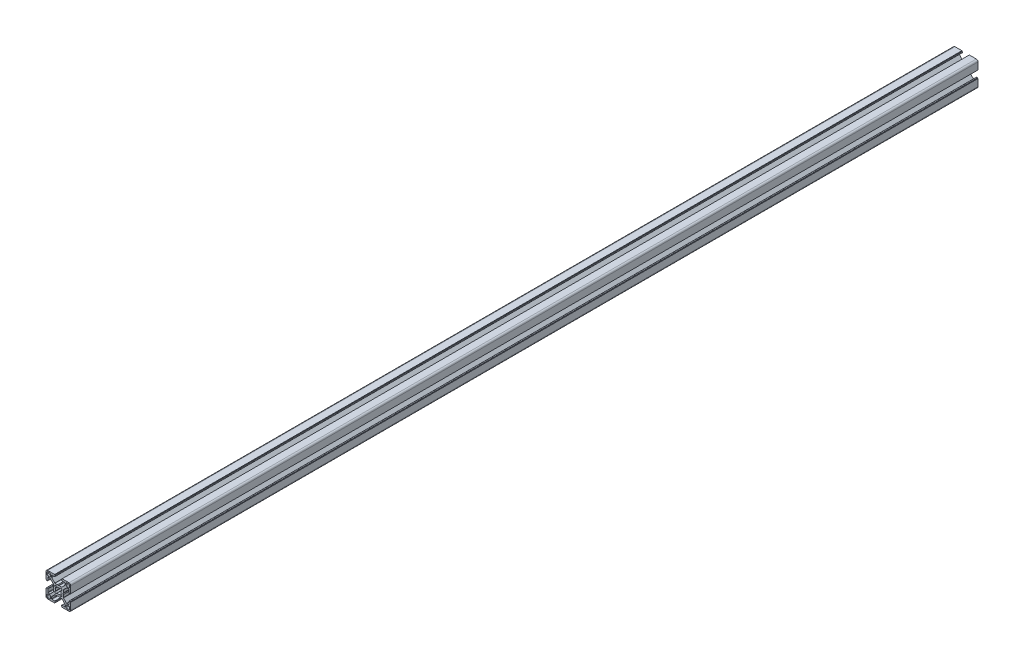
SolidWorks part; units mm, degrees
ref_plane "Front Plane" through (0, 0, 0) normal (0, 0, 1) x (1, 0, 0)
ref_plane "Top Plane" through (0, 0, 0) normal (0, 1, 0) x (1, 0, 0)
ref_plane "Right Plane" through (0, 0, 0) normal (1, 0, 0) x (0, 0, -1)
sketch "Sketch1" plane through (0, 0, 0) normal (0, 0, 1) x (1, 0, 0)
  line L0 (-15, 0) -> (15, 0) construction
  line L1 (0, -15) -> (0, 15) construction
  line L2 (-4.5, 15) -> (4.5, 15) construction
  line L3 (-4, -15) -> (4, -15) construction
  line L4 (-4.5, 15) -> (-4.5, 14.5)
  line L5 (-4.5, 14.5) -> (-4, 14.5)
  line L6 (-4, 14.5) -> (-4, 13.29)
  line L7 (-4.5, 12.79) -> (-7.7675, 12.79)
  line L8 (-8.2675, 12.29) -> (-8.2675, 10.2707)
  line L9 (-8.1211, 9.9171) -> (-4.3504, 6.1464)
  line L10 (-3.9968, 6) -> (0, 6)
  line L11 (0, 0) -> (-15, 15) construction
  line L12 (-4.5, 15) -> (-12.968, 15)
  line L14 (-12.705, 9.5135) -> (-10.5135, 9.5135)
  line L15 (-13.705, 10.5135) -> (-13.705, 12.705)
  line L16 (-12.705, 13.705) -> (-10.5135, 13.705)
  line L17 (-9.5135, 10.5135) -> (-9.5135, 12.705)
  line L18 (-13.705, 9.5135) -> (-9.5135, 13.705) construction
  line L19 (-13.705, 13.705) -> (-9.5135, 9.5135) construction
  line L20 (-3.1568, 4.5038) -> (-1.5303, 3.1477) construction
  line L21 (-4.5038, 3.1568) -> (-3.1477, 1.5303) construction
  line L22 (-6, 3.9968) -> (-6, 0)
  line L23 (-9.9171, 8.1211) -> (-6.1464, 4.3504)
  line L24 (-15, 4.5) -> (-15, 12.968)
  line L25 (-12.29, 8.2675) -> (-10.2707, 8.2675)
  line L26 (-12.79, 4.5) -> (-12.79, 7.7675)
  line L27 (-14.5, 4) -> (-13.29, 4)
  line L28 (-14.5, 4.5) -> (-14.5, 4)
  line L29 (-15, 4.5) -> (-14.5, 4.5)
  circle A0 centre (0, 0) radius 3.5
  arc A1 (-12.968, 15) -> (-15, 12.968) centre (-12.968, 12.968) ccw
  circle A2 centre (0, 0) radius 5.5 construction
  arc A3 (-10.5135, 9.5135) -> (-9.5135, 10.5135) centre (-10.5135, 10.5135) ccw
  arc A4 (-13.705, 12.705) -> (-12.705, 13.705) centre (-12.705, 12.705) cw
  arc A5 (-10.5135, 13.705) -> (-9.5135, 12.705) centre (-10.5135, 12.705) cw
  arc A6 (-12.705, 9.5135) -> (-13.705, 10.5135) centre (-12.705, 10.5135) cw
  arc A7 (-12.79, 4.5) -> (-13.29, 4) centre (-13.29, 4.5) cw
  arc A8 (-12.29, 8.2675) -> (-12.79, 7.7675) centre (-12.29, 7.7675) ccw
  arc A9 (-9.9171, 8.1211) -> (-10.2707, 8.2675) centre (-10.2707, 7.7675) ccw
  arc A10 (-6, 3.9968) -> (-6.1464, 4.3504) centre (-6.5, 3.9968) ccw
  arc A11 (-4.3504, 6.1464) -> (-3.9968, 6) centre (-3.9968, 6.5) ccw
  arc A12 (-4, 13.29) -> (-4.5, 12.79) centre (-4.5, 13.29) cw
  arc A13 (-7.7675, 12.79) -> (-8.2675, 12.29) centre (-7.7675, 12.29) ccw
  arc A14 (-8.2675, 10.2707) -> (-8.1211, 9.9171) centre (-7.7675, 10.2707) ccw
  point P4 (0, 0)
  point P8 (0, 0)
  point P13 (0, 15)
  point P15 (0, -15)
  point P16 (0, 6)
  point P23 (-11.6092, 11.6093)
  point P26 (0, 6)
  point P62 (-12.79, 4)
  point P65 (-12.79, 8.2675)
  point P68 (-10.0636, 8.2675)
  point P71 (-6, 4.2039)
  point P74 (-4.2039, 6)
  point P77 (-4, 12.79)
  point P80 (-8.2675, 12.79)
  point P83 (-8.2675, 10.0636)
  dimension "Center Hole Diameter" = 7
  dimension "D11" = 2.032
  dimension "D9" = 11
  dimension "D13" = 1
  dimension "D14" = 0.5
  dimension "Rail Height" = 30
  dimension "Rail Width" = 30
  dimension "T-Slot Width" = 8
  dimension "T-Slot Depth" = 9
  dimension "D1" = 9
  dimension "D2" = 45
  dimension "D3" = 8
  dimension "D4" = 2.21
  dimension "D5" = 16.535
  dimension "D7" = 2.54
  dimension "D6" = 1.295
  dimension "D8" = 1.246
  dimension "D10" = 10.36
  dimension "D12" = 1.905
sketch "Sketch2" plane through (0, 0, 0) normal (1, 0, 0) x (0, 0, -1)
  line L0 (-76.2, 0) -> (76.2, 0) construction
  line L2 (0, -15) -> (0, 15) construction
  line L3 (0, -15) -> (0, 15) construction
  line L4 (-76.2, -15) -> (-76.2, 15) construction
  line L5 (76.2, -15) -> (76.2, 15) construction
  point P0 (-38.7, 0)
  point P3 (0, 0)
  point P4 (38.7, 0)
  point P12 (-76.2, 0)
  point P14 (76.2, 0)
  dimension "Length" = 152.4
  dimension "D1" = 37.5
sketch "Sketch3" plane through (0, 0, 0) normal (0, 0, 1) x (1, 0, 0)
  line L0 (-4.5038, 3.1568) -> (-3.1477, 1.5303)
  line L1 (0, 3.5) -> (0, 5.5)
  line L2 (-5.5, 0) -> (-3.5, 0)
  line L7 (-6, 3.9968) -> (-6, 0) construction
  line L31 (-9.9171, 8.1211) -> (-6.1464, 4.3504) construction
  line L117 (-12.29, 8.2675) -> (-10.2707, 8.2675) construction
  line L118 (-12.79, 4.5) -> (-12.79, 7.7675) construction
  line L157 (-12.705, 9.5135) -> (-10.5135, 9.5135)
  line L158 (-9.5135, 10.5135) -> (-9.5135, 12.705)
  line L163 (-10.5135, 13.705) -> (-12.705, 13.705)
  line L164 (-13.705, 12.705) -> (-13.705, 10.5135)
  line L165 (-12.705, 9.5135) -> (-10.5135, 9.5135)
  line L166 (-9.5135, 10.5135) -> (-9.5135, 12.705)
  line L167 (-10.5135, 13.705) -> (-12.705, 13.705)
  line L168 (-13.705, 12.705) -> (-13.705, 10.5135)
  line L169 (-14.5, 4) -> (-13.29, 4) construction
  line L170 (-14.5, 4.5) -> (-14.5, 4) construction
  line L171 (-15, 4.5) -> (-14.5, 4.5) construction
  line L172 (-15, 4.5) -> (-15, 12.968) construction
  line L173 (-4.5, 15) -> (-12.968, 15) construction
  line L174 (-4.5, 15) -> (-4.5, 14.5) construction
  line L175 (-4.5, 14.5) -> (-4, 14.5) construction
  line L176 (-4, 14.5) -> (-4, 13.29) construction
  line L177 (-4.5, 12.79) -> (-7.7675, 12.79) construction
  line L178 (-8.2675, 12.29) -> (-8.2675, 10.2707) construction
  line L179 (-8.1211, 9.9171) -> (-4.3504, 6.1464) construction
  line L180 (-3.9968, 6) -> (0, 6) construction
  line L181 (-6, 3.9968) -> (-6, 0.866)
  line L182 (-9.9171, 8.1211) -> (-6.1464, 4.3504)
  line L183 (-12.29, 8.2675) -> (-10.2707, 8.2675)
  line L184 (-12.79, 4.5) -> (-12.79, 7.7675)
  line L185 (-14.5, 4) -> (-13.29, 4)
  line L186 (-14.5, 4.5) -> (-14.5, 4)
  line L187 (-15, 4.5) -> (-14.5, 4.5)
  line L188 (-15, 4.5) -> (-15, 12.968)
  line L189 (-4.5, 15) -> (-12.968, 15)
  line L190 (-4.5, 15) -> (-4.5, 14.5)
  line L191 (-4.5, 14.5) -> (-4, 14.5)
  line L192 (-4, 14.5) -> (-4, 13.29)
  line L193 (-4.5, 12.79) -> (-7.7675, 12.79)
  line L194 (-8.2675, 12.29) -> (-8.2675, 10.2707)
  line L195 (-8.1211, 9.9171) -> (-4.3504, 6.1464)
  line L196 (-3.9968, 6) -> (-0.866, 6)
  line L197 (-0.866, 6) -> (0, 5.5)
  line L198 (0, -15) -> (0, 15) construction
  line L199 (0, 0) -> (-15, 15) construction
  line L200 (0, 0) -> (-15, 15) construction
  line L201 (-3.1568, 4.5038) -> (-1.5303, 3.1477) construction
  line L202 (-3.1568, 4.5038) -> (-1.5303, 3.1477)
  line L203 (-6, 0.866) -> (-5.5, 0)
  line L204 (-15, 0) -> (15, 0) construction
  line L205 (-15, 0) -> (15, 0) construction
  line L206 (0, -15) -> (0, 15) construction
  arc A0 (-3.5, 0) -> (-3.1477, 1.5303) centre (0, 0) cw
  arc A10 (-6, 3.9968) -> (-6.1464, 4.3504) centre (-6.5, 3.9968) ccw construction
  circle A16 centre (0, 0) radius 3.5
  arc A18 (0, 3.5) -> (-1.5303, 3.1477) centre (0, 0) ccw
  arc A20 (-9.9171, 8.1211) -> (-10.2707, 8.2675) centre (-10.2707, 7.7675) ccw construction
  arc A22 (-12.29, 8.2675) -> (-12.79, 7.7675) centre (-12.29, 7.7675) ccw construction
  arc A28 (-13.29, 4) -> (-12.79, 4.5) centre (-13.29, 4.5) ccw construction
  arc A29 (-10.5135, 9.5135) -> (-9.5135, 10.5135) centre (-10.5135, 10.5135) ccw
  arc A30 (-9.5135, 12.705) -> (-10.5135, 13.705) centre (-10.5135, 12.705) ccw
  arc A31 (-12.705, 13.705) -> (-13.705, 12.705) centre (-12.705, 12.705) ccw
  arc A32 (-13.705, 10.5135) -> (-12.705, 9.5135) centre (-12.705, 10.5135) ccw
  arc A33 (-10.5135, 9.5135) -> (-9.5135, 10.5135) centre (-10.5135, 10.5135) ccw
  arc A34 (-9.5135, 12.705) -> (-10.5135, 13.705) centre (-10.5135, 12.705) ccw
  arc A35 (-12.705, 13.705) -> (-13.705, 12.705) centre (-12.705, 12.705) ccw
  arc A36 (-13.705, 10.5135) -> (-12.705, 9.5135) centre (-12.705, 10.5135) ccw
  arc A37 (-12.968, 15) -> (-15, 12.968) centre (-12.968, 12.968) ccw construction
  arc A38 (-4.5, 12.79) -> (-4, 13.29) centre (-4.5, 13.29) ccw construction
  arc A39 (-7.7675, 12.79) -> (-8.2675, 12.29) centre (-7.7675, 12.29) ccw construction
  arc A40 (-8.2675, 10.2707) -> (-8.1211, 9.9171) centre (-7.7675, 10.2707) ccw construction
  arc A41 (-4.3504, 6.1464) -> (-3.9968, 6) centre (-3.9968, 6.5) ccw construction
  arc A42 (-6, 3.9968) -> (-6.1464, 4.3504) centre (-6.5, 3.9968) ccw
  arc A43 (-9.9171, 8.1211) -> (-10.2707, 8.2675) centre (-10.2707, 7.7675) ccw
  arc A44 (-12.29, 8.2675) -> (-12.79, 7.7675) centre (-12.29, 7.7675) ccw
  arc A45 (-13.29, 4) -> (-12.79, 4.5) centre (-13.29, 4.5) ccw
  arc A46 (-12.968, 15) -> (-15, 12.968) centre (-12.968, 12.968) ccw
  arc A47 (-4.5, 12.79) -> (-4, 13.29) centre (-4.5, 13.29) ccw
  arc A48 (-7.7675, 12.79) -> (-8.2675, 12.29) centre (-7.7675, 12.29) ccw
  arc A49 (-8.2675, 10.2707) -> (-8.1211, 9.9171) centre (-7.7675, 10.2707) ccw
  arc A50 (-4.3504, 6.1464) -> (-3.9968, 6) centre (-3.9968, 6.5) ccw
  circle A51 centre (0, 0) radius 5.5 construction
  arc A52 (-3.1568, 4.5038) -> (-4.5038, 3.1568) centre (0, 0) ccw
  dimension "D3" = 60
  dimension "D4" = 60
  dimension "D1" = 0
  dimension "D2" = 0
extrude "Boss-Extrude1" add sketch "Sketch3" along normal mid plane 1100
pattern_circular "CirPattern1" count 4 over 360 about axis through (0, 0, 76.2) along (0, 0, -1) of "Boss-Extrude1"
ref_plane "Contact Plane1" through (15, 0, 0) normal (1, 0, 0) x (0, 0, -1)
ref_plane "Contact Plane2" through (0, -15, 0) normal (0, 1, 0) x (1, 0, 0)
ref_plane "Contact Plane3" through (-15, 0, 0) normal (1, 0, 0) x (0, 0, -1)
ref_plane "Contact Plane4" through (0, 15, 0) normal (0, 1, 0) x (1, 0, 0)
equation "\"D1@Sketch2\" = \"Rail Height@Sketch1\" * 1.25"
equation "\"D1@Sketch1\"=\"T-Slot Width@Sketch1\"+1mm"
equation "\"D3@Sketch1\"=\"T-Slot Width@Sketch1\""
equation "\"D1@Boss-Extrude1\"=\"length\""
equation "\"length\" = 1100"
